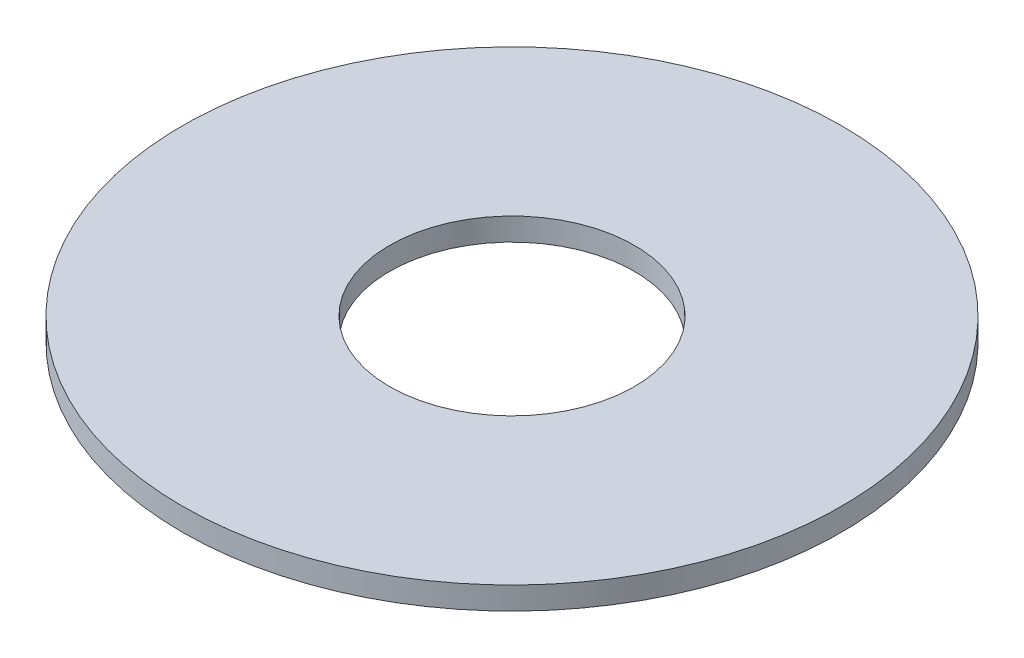
SolidWorks part; units mm, degrees
ref_plane "Front Plane" through (0, 0, 0) normal (0, 0, 1) x (1, 0, 0)
ref_plane "Top Plane" through (0, 0, 0) normal (0, 1, 0) x (1, 0, 0)
ref_plane "Right Plane" through (0, 0, 0) normal (1, 0, 0) x (0, 0, -1)
sketch "Sketch1" plane through (0, 0, 0) normal (0, 1, 0) x (1, 0, 0)
  circle A0 centre (0, 0) radius 87.5
  dimension "FLANGE_OD" = 175
extrude "Boss-Extrude1" add sketch "Sketch1" along normal blind 6
sketch "Sketch2" plane through (0, 0, 0) normal (0, 1, 0) x (1, 0, 0)
  circle A0 centre (0, 0) radius 32.5
  dimension "BORE_D" = 65
extrude "Cut-Extrude1" cut sketch "Sketch2" along normal through all
sketch "Sketch3" plane through (0, 6, 0) normal (0, 1, 0) x (1, 0, 0)
  circle A0 centre (0, 0) radius 23.7033 construction
  circle A1 centre (-23.7033, 0) radius 1.9777
  dimension "BOLT_D" = 3.9554
  dimension "BOLT_PCD" = 47.4066
extrude "Cut-Extrude2" cut sketch "Sketch3" against normal blind 4.1809 rebuild error yes
pattern_circular "CirPattern1" count 6 over 360 rebuild error yes
